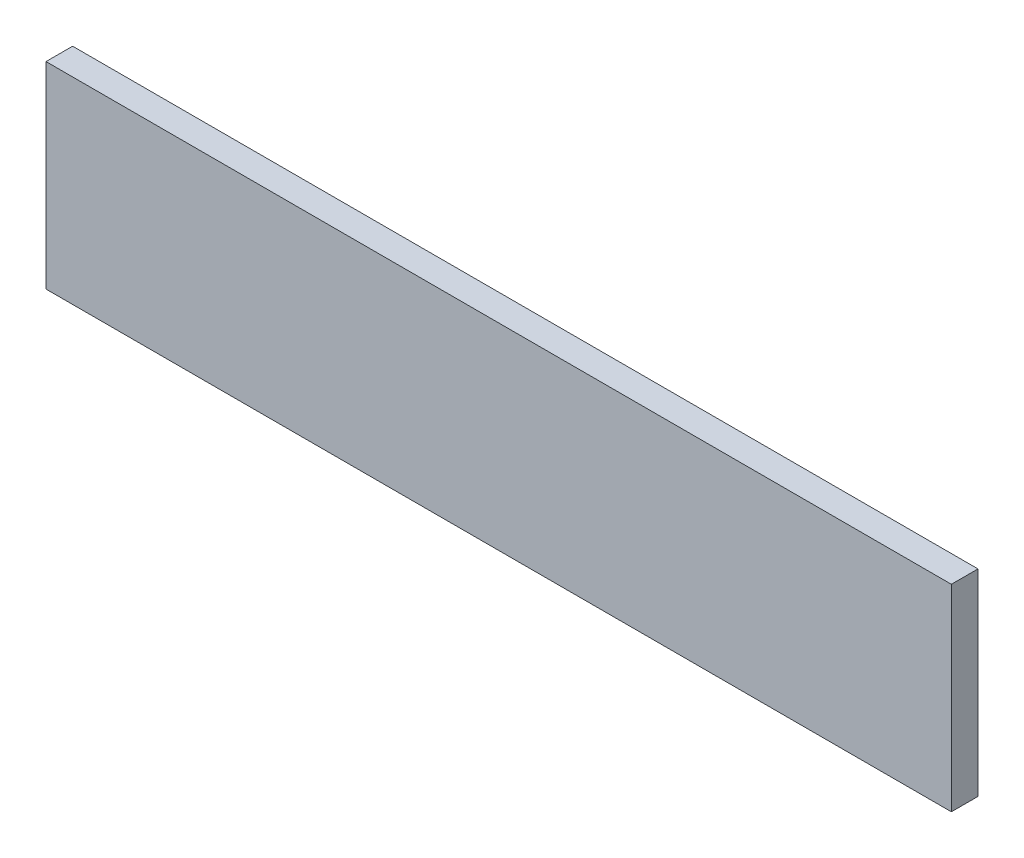
SolidWorks part; units mm, degrees
material "Plain Carbon Steel"
ref_plane "Front Plane" through (0, 0, 0) normal (0, 0, 1) x (1, 0, 0)
ref_plane "Top Plane" through (0, 0, 0) normal (0, 1, 0) x (1, 0, 0)
ref_plane "Right Plane" through (0, 0, 0) normal (1, 0, 0) x (0, 0, -1)
sketch "Sketch1" plane through (0, 0, 0) normal (0, 0, 1) x (1, 0, 0)
  line L0 (80, -37.7497) -> (80, 151.1829) construction
  line L1 (-90, 67) -> (250, 67)
  line L2 (-90, 67) -> (-90, -7)
  line L3 (-90, -7) -> (250, -7)
  line L4 (250, 67) -> (250, -7)
  line L7 (-70, 5) -> (-70, 65) construction
  line L8 (-67, 67) -> (227, 67) construction
  line L9 (227, -7) -> (-67, -7) construction
  point P4 (80, 67)
  dimension "D3" = 20
extrude "Boss-Extrude1" add sketch "Sketch1" along normal blind 10
